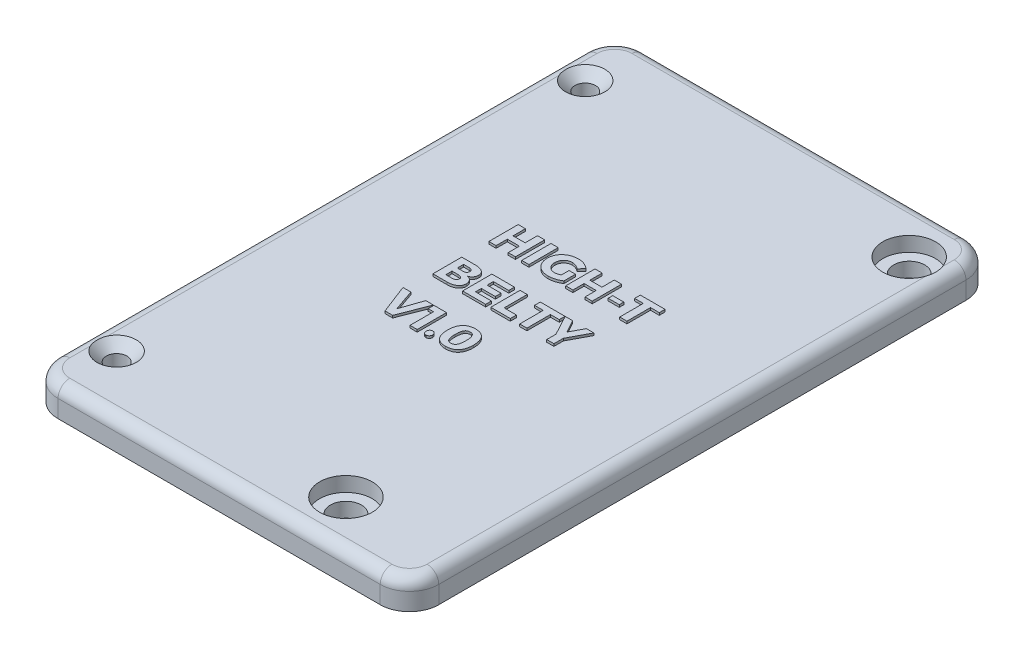
SolidWorks part; units mm, degrees
ref_plane "Front Plane" through (0, 0, 0) normal (0, 0, 1) x (1, 0, 0)
ref_plane "Top Plane" through (0, 0, 0) normal (0, 1, 0) x (1, 0, 0)
ref_plane "Right Plane" through (0, 0, 0) normal (1, 0, 0) x (0, 0, -1)
sketch "Sketch2" plane through (0, 0, 0) normal (0, 1, 0) x (1, 0, 0)
  line L1 (-32.5, 50) -> (32.5, 50)
  line L2 (-32.5, 50) -> (-32.5, -50)
  line L3 (-32.5, -50) -> (32.5, -50)
  line L4 (32.5, 50) -> (32.5, -50)
  line L5 (-32.5, 50) -> (32.5, -50) construction
  line L6 (-32.5, -50) -> (32.5, 50) construction
  circle A0 centre (-27.5, 40) radius 1.75
  circle A1 centre (-27.5, -40) radius 1.75
  circle A2 centre (26.23, 41.58) radius 2.65
  circle A3 centre (13.65, -42) radius 2.65
  point P0 (0, 0)
  dimension "D3" = 3.5
  dimension "D4" = 5
  dimension "D8" = 5.3
  dimension "D9" = 5.3
  dimension "D1" = 65
  dimension "D2" = 100
  dimension "D5" = 5
  dimension "D6" = 10
  dimension "D7" = 10
  dimension "D10" = 46.15
  dimension "D11" = 8
  dimension "D12" = 8.42
  dimension "D13" = 6.27
extrude "Boss-Extrude1" add sketch "Sketch2" along normal blind 5
sketch "Sketch3" plane through (0, 5, 0) normal (0, 1, 0) x (1, 0, 0)
  circle A0 centre (26.23, 41.58) radius 4.5
  circle A1 centre (13.65, -42) radius 4.5
  dimension "D1" = 9
  dimension "D2" = 9
extrude "Cut-Extrude1" cut sketch "Sketch3" against normal blind 2.5
fillet "Fillet1" radius 5 4 edges at (-32.5, 2.5, 50) (-32.5, 2.5, -50) (32.5, 2.5, -50) (32.5, 2.5, 50)
chamfer "Chamfer1" distance 1.6 angle 45 2 edges at (-27.5, 5, 41.75) (-27.5, 5, -38.25)
fillet "Fillet2" radius 2 8 edges at (-31.0355, 5, 48.5355) (-32.5, 5, 0) (-31.0355, 5, -48.5355) (0, 5, -50) (31.0355, 5, -48.5355) (32.5, 5, 0) (31.0355, 5, 48.5355) (0, 5, 50)
sketch "Sketch4" plane through (0, 5, 0) normal (0, 1, 0) x (1, 0, 0)
  text T0 "<b>HIGH-T</b>\r\n<b>BELTY</b>\r\n<b>V1.0</b>" font "Montserrat" height 5
  point P1 (-19.1917, -1.3015)
  point P2 (0, 0)
  point P3 (-19.1203, -1.7707)
  point P4 (-19.8626, -1.8473)
  point P5 (-12.0717, 7.5852)
extrude "Boss-Extrude2" add sketch "Sketch4" along normal blind 0.4
